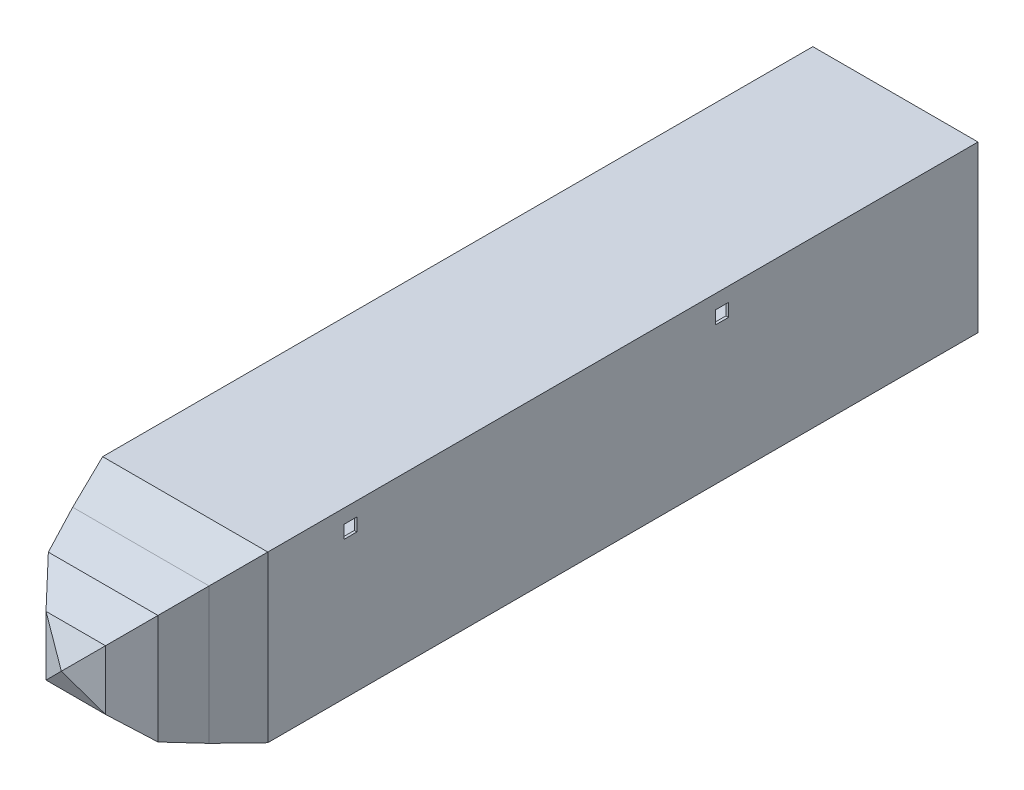
SolidWorks part; units mm, degrees
ref_plane "Front Plane" through (0, 0, 0) normal (0, 0, 1) x (1, 0, 0)
ref_plane "Top Plane" through (0, 0, 0) normal (0, 1, 0) x (1, 0, 0)
ref_plane "Right Plane" through (0, 0, 0) normal (1, 0, 0) x (0, 0, -1)
sketch "Sketch1" plane through (0, 0, 0) normal (0, 0, 1) x (1, 0, 0)
  line L1 (-50.8, -50.8) -> (50.8, -50.8)
  line L2 (-50.8, -50.8) -> (-50.8, 50.8)
  line L3 (-50.8, 50.8) -> (50.8, 50.8)
  line L4 (50.8, -50.8) -> (50.8, 50.8)
  line L5 (-50.8, -50.8) -> (50.8, 50.8) construction
  line L6 (-50.8, 50.8) -> (50.8, -50.8) construction
  point P0 (0, 0)
  dimension "D1" = 101.6
  dimension "D2" = 101.6
extrude "Boss-Extrude1" add sketch "Sketch1" along normal blind 436.88 contours L2 L1 L4 L3
ref_plane "Plane1" through (0, 0, 464.1566) normal (0, 0, 1) x (1, 0, 0)
sketch "Sketch3" plane through (0, 0, 464.1566) normal (0, 0, 1) x (1, 0, 0)
  line L1 (-41.9373, -41.9373) -> (41.9373, -41.9373)
  line L2 (-41.9373, -41.9373) -> (-41.9373, 41.9373)
  line L3 (-41.9373, 41.9373) -> (41.9373, 41.9373)
  line L4 (41.9373, -41.9373) -> (41.9373, 41.9373)
  line L5 (-41.9373, -41.9373) -> (41.9373, 41.9373) construction
  line L6 (-41.9373, 41.9373) -> (41.9373, -41.9373) construction
  point P0 (0, 0)
  dimension "D1" = 83.8746
  dimension "D2" = 83.8746
sketch "Sketch5" plane through (0, 0, 436.88) normal (0, 0, 1) x (1, 0, 0)
  line L0 (50.8, -50.8) -> (50.8, 50.8) construction
  line L1 (-50.8, 50.8) -> (50.8, 50.8) construction
  line L2 (-50.8, -50.8) -> (-50.8, 50.8) construction
  line L3 (-50.8, -50.8) -> (50.8, -50.8) construction
  line L4 (50.8, -50.8) -> (50.8, 50.8)
  line L5 (-50.8, 50.8) -> (50.8, 50.8)
  line L6 (-50.8, -50.8) -> (-50.8, 50.8)
  line L7 (-50.8, -50.8) -> (50.8, -50.8)
  dimension "D1" = 101.6
  dimension "D2" = 101.6
loft "Loft2" add profiles "Sketch5", "Sketch3" connector at (-50.8, 50.8, 436.88) connector at (-41.9373, 41.9373, 464.1566)
ref_plane "Plane2" through (0, 0, 487.3594) normal (0, 0, 1) x (1, 0, 0)
sketch "Sketch6" plane through (0, 0, 487.3594) normal (0, 0, 1) x (1, 0, 0)
  line L1 (-33.716, -33.716) -> (33.716, -33.716)
  line L2 (-33.716, -33.716) -> (-33.716, 33.716)
  line L3 (-33.716, 33.716) -> (33.716, 33.716)
  line L4 (33.716, -33.716) -> (33.716, 33.716)
  line L5 (-33.716, -33.716) -> (33.716, 33.716) construction
  line L6 (-33.716, 33.716) -> (33.716, -33.716) construction
  point P0 (0, 0)
loft "Loft3" add profiles "Sketch3<6>", "Sketch6" connector at (-41.9373, 41.9373, 464.1566) connector at (-33.716, 33.716, 487.3594)
sketch "Sketch3<6>" plane through (0, 0, 464.1566) normal (0, 0, 1) x (1, 0, 0) same geometry as "Sketch3"
ref_plane "Plane3" through (0, 0, 504.2173) normal (0, 0, 1) x (1, 0, 0)
sketch "Sketch7" plane through (0, 0, 504.2173) normal (0, 0, 1) x (1, 0, 0)
  line L5 (-41.9373, -41.9373) -> (41.9373, 41.9373) construction
  line L6 (-18.3041, -18.3041) -> (18.3041, -18.3041)
  line L8 (-18.3041, -18.3041) -> (-18.3041, 18.3041)
  line L9 (-18.3041, 18.3041) -> (18.3041, 18.3041)
  line L10 (18.3041, -18.3041) -> (18.3041, 18.3041)
  line L11 (-18.3041, -18.3041) -> (18.3041, 18.3041) construction
  line L12 (-18.3041, 18.3041) -> (18.3041, -18.3041) construction
  point P1 (0, 0)
loft "Loft4" add profiles "Sketch6<4>", "Sketch7" connector at (33.716, 33.716, 487.3594) connector at (18.3041, 18.3041, 504.2173)
sketch "Sketch6<4>" plane through (0, 0, 487.3594) normal (0, 0, 1) x (1, 0, 0) same geometry as "Sketch6"
sketch3d "3DSketch1" plane through (0, 0, 0) normal (0, 0, 1) x (1, 0, 0)
  dimension "D1" = 8.8627
sketch "Sketch8" plane through (0, 0, 513.08) normal (0, 0, 1) x (1, 0, 0)
  point P0 (0, 0)
loft "Loft5" add profiles "Sketch8", "Sketch7<5>"
sketch "Sketch7<5>" plane through (0, 0, 504.2173) normal (0, 0, 1) x (1, 0, 0) same geometry as "Sketch7"
shell "Shell1" thickness 1.5875 removed face at (0, 0, 0)
sketch "Sketch9" plane through (50.8, 0, 0) normal (1, 0, 0) x (0, 0, -1)
  line L0 (-436.88, 50.8) -> (-436.88, 38.1)
  line L1 (-436.88, -50.8) -> (-436.88, 50.8) construction
  line L2 (-436.88, 38.1) -> (-386.08, 38.1)
  line L3 (-386.08, 38.1) -> (-157.48, 38.1)
  line L5 (-390.0805, 34.0995) -> (-382.0795, 34.0995)
  line L6 (-390.0805, 34.0995) -> (-390.0805, 42.1005)
  line L7 (-390.0805, 42.1005) -> (-382.0795, 42.1005)
  line L8 (-382.0795, 34.0995) -> (-382.0795, 42.1005)
  line L9 (-390.0805, 34.0995) -> (-382.0795, 42.1005) construction
  line L10 (-390.0805, 42.1005) -> (-382.0795, 34.0995) construction
  line L11 (-161.4805, 34.0995) -> (-153.4795, 34.0995)
  line L12 (-161.4805, 34.0995) -> (-161.4805, 42.1005)
  line L13 (-161.4805, 42.1005) -> (-153.4795, 42.1005)
  line L14 (-153.4795, 34.0995) -> (-153.4795, 42.1005)
  line L15 (-161.4805, 34.0995) -> (-153.4795, 42.1005) construction
  line L16 (-161.4805, 42.1005) -> (-153.4795, 34.0995) construction
  dimension "D4" = 8.001
  dimension "D5" = 8.001
  dimension "D1" = 12.7
  dimension "D2" = 50.8
  dimension "D3" = 228.6
  dimension "D6" = 8.001
  dimension "D7" = 8.001
extrude "Cut-Extrude1" cut sketch "Sketch9" against normal through all contours L5 L8 L3 L2 L6 | L3 L8 L7 L6 L2 | L11 L14 L13 L12 region at (50.8, 40.1002, 386.08) region at (50.8, 36.0997, 386.08) region at (50.8, 40.1002, 161.3673)
equation "\"Fuse_Diam\"= 4"
equation "\"D2@Sketch1\"=\"Fuse_Diam\""
equation "\"D1@Sketch1\"=\"Fuse_Diam\""
equation "\"Magic Line\"= 3 / ( cos ( 18 ) + cos ( 2 * 18 ) + cos ( 3 * 18 ) + cos ( 4 * 18 ) )"
equation "\"Second Stage Cone\"=3.30215"
equation "\"D1@Sketch3\"=\"Second Stage Cone\""
equation "\"D2@Sketch3\"=\"Second Stage Cone\""
